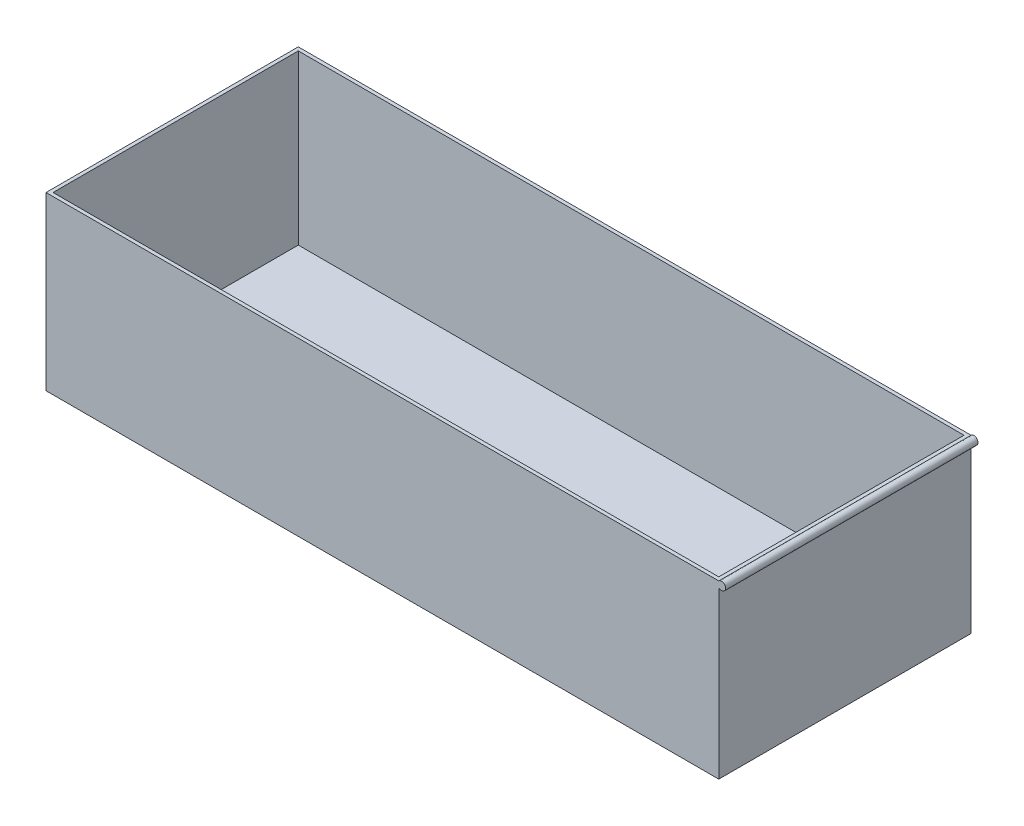
SolidWorks part; units mm, degrees
material "ASTM A36 Steel"
ref_plane "Front Plane" through (0, 0, 0) normal (0, 0, 1) x (1, 0, 0)
ref_plane "Top Plane" through (0, 0, 0) normal (0, 1, 0) x (1, 0, 0)
ref_plane "Right Plane" through (0, 0, 0) normal (1, 0, 0) x (0, 0, -1)
sketch "Sketch1" plane through (0, 0, 0) normal (0, 1, 0) x (1, 0, 0)
  line L1 (152.4, 57.15) -> (-152.4, 57.15)
  line L2 (152.4, 57.15) -> (152.4, -57.15)
  line L3 (152.4, -57.15) -> (-152.4, -57.15)
  line L4 (-152.4, 57.15) -> (-152.4, -57.15)
  line L5 (152.4, 57.15) -> (-152.4, -57.15) construction
  line L6 (152.4, -57.15) -> (-152.4, 57.15) construction
  point P0 (0, 0)
  dimension "D1" = 114.3
  dimension "D2" = 304.8
extrude "Boss-Extrude1" add sketch "Sketch1" along normal blind 1.5875
sketch "Sketch2" plane through (0, 1.5875, 0) normal (0, 1, 0) x (1, 0, 0)
  line L8 (-150.8125, 55.5625) -> (-150.8125, -55.5625)
  line L9 (-150.8125, -55.5625) -> (150.8125, -55.5625)
  line L10 (150.8125, -55.5625) -> (150.8125, 55.5625)
  line L11 (150.8125, 55.5625) -> (-150.8125, 55.5625)
  line L12 (-150.8125, 55.5625) -> (-150.8125, -55.5625)
  line L13 (-150.8125, -55.5625) -> (150.8125, -55.5625)
  line L14 (150.8125, -55.5625) -> (150.8125, 55.5625)
  line L15 (150.8125, 55.5625) -> (-150.8125, 55.5625)
  line L16 (-152.4, 57.15) -> (-152.4, -57.15)
  line L17 (-152.4, -57.15) -> (152.4, -57.15)
  line L18 (152.4, -57.15) -> (152.4, 57.15)
  line L19 (152.4, 57.15) -> (-152.4, 57.15)
  line L20 (-152.4, 57.15) -> (-152.4, -57.15)
  line L21 (-152.4, -57.15) -> (152.4, -57.15)
  line L22 (152.4, -57.15) -> (152.4, 57.15)
  line L23 (152.4, 57.15) -> (-152.4, 57.15)
  dimension "D1" = 1.5875
  dimension "D2" = 0
extrude "Boss-Extrude2" add sketch "Sketch2" along normal blind 76.2
sketch "Sketch3" plane through (0, 0, 0) normal (0, 0, 1) x (1, 0, 0)
  line L0 (152.4, 77.7875) -> (152.4, 0) construction
  line L1 (152.4, 77.7875) -> (152.4, 0)
  arc A0 (152.4, 77.7875) -> (152.4, 75.18) centre (153.7037, 76.4838) cw
  dimension "D1" = 1.8438
  dimension "D2" = 1.3037
extrude "Boss-Extrude3" add sketch "Sketch3" along normal mid plane 114.3 contours A0 L1 region at (153.8559, 76.4838, 0)
